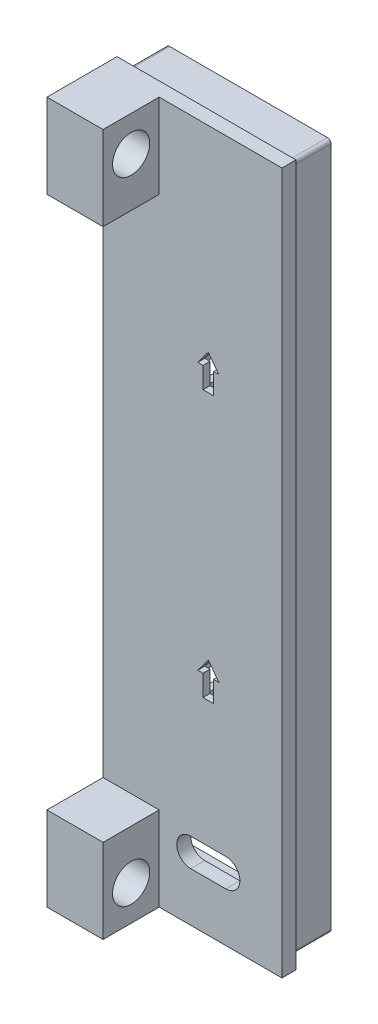
SolidWorks part; units mm, degrees
ref_plane "Front Plane" through (0, 0, 0) normal (0, 0, 1) x (1, 0, 0)
ref_plane "Top Plane" through (0, 0, 0) normal (0, 1, 0) x (1, 0, 0)
ref_plane "Right Plane" through (0, 0, 0) normal (1, 0, 0) x (0, 0, -1)
sketch "Sketch1" plane through (0, 0, 0) normal (0, 0, 1) x (1, 0, 0)
  line L0 (15.5, 38) -> (-15.5, 38) construction
  line L1 (40, 50) -> (-40, 50)
  line L2 (40, 50) -> (40, -50)
  line L3 (40, -50) -> (-40, -50)
  line L4 (-40, 50) -> (-40, -50)
  line L5 (0, 50) -> (0, -50) construction
  line L6 (15.5, 43.5) -> (15.5, 32.5)
  line L7 (15.5, -38) -> (-15.5, -38) construction
  line L260 (15.5, 43.5) -> (-15.5, 43.5)
  line L261 (15.5, 5.5) -> (-15.5, 5.5)
  line L262 (15.5, 5.5) -> (15.5, -5.5)
  line L263 (15.5, -5.5) -> (-15.5, -5.5)
  line L264 (-15.5, 5.5) -> (-15.5, -5.5)
  line L265 (0, -5.5) -> (0, 5.5) construction
  line L266 (15.5, 0) -> (-15.5, 0) construction
  line L271 (-15.5, 43.5) -> (-15.5, 32.5)
  line L272 (15.5, 32.5) -> (-15.5, 32.5)
  line L277 (15.5, -32.5) -> (15.5, -43.5)
  line L278 (15.5, -32.5) -> (-15.5, -32.5)
  line L283 (-15.5, -32.5) -> (-15.5, -43.5)
  line L284 (15.5, -43.5) -> (-15.5, -43.5)
  line L289 (25, 50) -> (25, -50) construction
  line L290 (7.7528, 32.5) -> (7.7528, 5.5) construction
  line L291 (30.5, 34.5) -> (19.5, 34.5)
  line L292 (30.5, 34.5) -> (30.5, 3.5)
  line L293 (30.5, 3.5) -> (19.5, 3.5)
  line L294 (19.5, 34.5) -> (19.5, 3.5)
  line L295 (25, 3.5) -> (25, 34.5) construction
  line L296 (30.5, 19) -> (19.5, 19) construction
  line L297 (-30.5, 3.5) -> (-19.5, 3.5)
  line L298 (-19.5, 34.5) -> (-19.5, 3.5)
  line L299 (-30.5, 34.5) -> (-19.5, 34.5)
  line L300 (-30.5, 34.5) -> (-30.5, 3.5)
  line L301 (-30.5, -34.5) -> (-30.5, -3.5)
  line L302 (-30.5, -34.5) -> (-19.5, -34.5)
  line L303 (-19.5, -34.5) -> (-19.5, -3.5)
  line L304 (-30.5, -3.5) -> (-19.5, -3.5)
  line L305 (30.5, -3.5) -> (19.5, -3.5)
  line L306 (19.5, -34.5) -> (19.5, -3.5)
  line L307 (30.5, -34.5) -> (19.5, -34.5)
  line L308 (30.5, -34.5) -> (30.5, -3.5)
  point P8 (0, 0)
  point P19 (25, 19)
  point P25 (7.7528, 19)
  dimension "D1" = 2
  dimension "D2" = 2
  dimension "D3" = 31
  dimension "D4" = 11
  dimension "D5" = 25
  dimension "D6" = 38
  dimension "D7" = 38
  dimension "D8" = 80
  dimension "D9" = 100
extrude "Boss-Extrude1" add sketch "Sketch1" along normal blind 1
sketch "Sketch2" plane through (0, 0, 1) normal (0, 0, 1) x (1, 0, 0)
  line L0 (40, 50) -> (-40, 50) construction
  line L1 (-40, 50) -> (-40, -50) construction
  line L2 (-40, -50) -> (40, -50) construction
  line L3 (40, -50) -> (40, 50) construction
  line L4 (40, 50) -> (-40, 50)
  line L5 (-40, 50) -> (-40, -50)
  line L6 (-40, -50) -> (40, -50)
  line L7 (40, -50) -> (40, 50)
extrude "back" add sketch "Sketch2" along normal blind 1
sketch "Sketch3" plane through (0, 0, 0) normal (0, 0, -1) x (-1, 0, 0)
  line L0 (-19.5, 3.5) -> (-19.5, 34.5) construction
  line L1 (-19.5, 34.5) -> (-30.5, 34.5) construction
  line L2 (-30.5, 34.5) -> (-30.5, 3.5) construction
  line L3 (-30.5, 3.5) -> (-19.5, 3.5) construction
  line L4 (15.5, -5.5) -> (15.5, 5.5) construction
  line L5 (15.5, 5.5) -> (-15.5, 5.5) construction
  line L6 (-15.5, 5.5) -> (-15.5, -5.5) construction
  line L7 (-15.5, -5.5) -> (15.5, -5.5) construction
  line L8 (-30.5, -3.5) -> (-30.5, -34.5) construction
  line L9 (-30.5, -34.5) -> (-19.5, -34.5) construction
  line L10 (-19.5, -34.5) -> (-19.5, -3.5) construction
  line L11 (-19.5, -3.5) -> (-30.5, -3.5) construction
  line L12 (-15.5, -43.5) -> (15.5, -43.5) construction
  line L13 (15.5, -43.5) -> (15.5, -32.5) construction
  line L14 (15.5, -32.5) -> (-15.5, -32.5) construction
  line L15 (-15.5, -32.5) -> (-15.5, -43.5) construction
  line L16 (19.5, -34.5) -> (30.5, -34.5) construction
  line L17 (30.5, -34.5) -> (30.5, -3.5) construction
  line L18 (30.5, -3.5) -> (19.5, -3.5) construction
  line L19 (19.5, -3.5) -> (19.5, -34.5) construction
  line L20 (30.5, 3.5) -> (30.5, 34.5) construction
  line L21 (30.5, 34.5) -> (19.5, 34.5) construction
  line L22 (19.5, 34.5) -> (19.5, 3.5) construction
  line L23 (19.5, 3.5) -> (30.5, 3.5) construction
  line L24 (-15.5, 32.5) -> (15.5, 32.5) construction
  line L25 (15.5, 32.5) -> (15.5, 43.5) construction
  line L26 (15.5, 43.5) -> (-15.5, 43.5) construction
  line L27 (-15.5, 43.5) -> (-15.5, 32.5) construction
  line L28 (15.5, -5.5) -> (15.5, 5.5)
  line L29 (15.5, 5.5) -> (-15.5, 5.5)
  line L30 (-15.5, 5.5) -> (-15.5, -5.5)
  line L31 (-15.5, -5.5) -> (15.5, -5.5)
  line L32 (-30.5, -3.5) -> (-30.5, -34.5)
  line L33 (-30.5, -34.5) -> (-19.5, -34.5)
  line L34 (-19.5, -34.5) -> (-19.5, -3.5)
  line L35 (-19.5, -3.5) -> (-30.5, -3.5)
  line L36 (-15.5, -43.5) -> (15.5, -43.5)
  line L37 (15.5, -43.5) -> (15.5, -32.5)
  line L38 (15.5, -32.5) -> (-15.5, -32.5)
  line L39 (-15.5, -32.5) -> (-15.5, -43.5)
  line L40 (19.5, -34.5) -> (30.5, -34.5)
  line L41 (30.5, -34.5) -> (30.5, -3.5)
  line L42 (30.5, -3.5) -> (19.5, -3.5)
  line L43 (19.5, -3.5) -> (19.5, -34.5)
  line L44 (30.5, 3.5) -> (30.5, 34.5)
  line L45 (30.5, 34.5) -> (19.5, 34.5)
  line L46 (19.5, 34.5) -> (19.5, 3.5)
  line L47 (19.5, 3.5) -> (30.5, 3.5)
  line L48 (-15.5, 32.5) -> (15.5, 32.5)
  line L49 (15.5, 32.5) -> (15.5, 43.5)
  line L50 (15.5, 43.5) -> (-15.5, 43.5)
  line L51 (-15.5, 43.5) -> (-15.5, 32.5)
  line L52 (-19.5, 3.5) -> (-19.5, 34.5)
  line L53 (-19.5, 34.5) -> (-30.5, 34.5)
  line L54 (-30.5, 34.5) -> (-30.5, 3.5)
  line L55 (-30.5, 3.5) -> (-19.5, 3.5)
  line L56 (-18.5, 2.5) -> (-18.5, 35.5)
  line L57 (-18.5, 35.5) -> (-31.5, 35.5)
  line L58 (-31.5, 35.5) -> (-31.5, 2.5)
  line L59 (-31.5, 2.5) -> (-18.5, 2.5)
  line L60 (-16.5, 31.5) -> (16.5, 31.5)
  line L61 (16.5, 31.5) -> (16.5, 44.5)
  line L62 (16.5, 44.5) -> (-16.5, 44.5)
  line L63 (-16.5, 44.5) -> (-16.5, 31.5)
  line L64 (31.5, 2.5) -> (31.5, 35.5)
  line L65 (31.5, 35.5) -> (18.5, 35.5)
  line L66 (18.5, 35.5) -> (18.5, 2.5)
  line L67 (18.5, 2.5) -> (31.5, 2.5)
  line L68 (16.5, -6.5) -> (16.5, 6.5)
  line L69 (16.5, 6.5) -> (-16.5, 6.5)
  line L70 (-16.5, 6.5) -> (-16.5, -6.5)
  line L71 (-16.5, -6.5) -> (16.5, -6.5)
  line L72 (-31.5, -2.5) -> (-31.5, -35.5)
  line L73 (-31.5, -35.5) -> (-18.5, -35.5)
  line L74 (-18.5, -35.5) -> (-18.5, -2.5)
  line L75 (-18.5, -2.5) -> (-31.5, -2.5)
  line L76 (-16.5, -44.5) -> (16.5, -44.5)
  line L77 (16.5, -44.5) -> (16.5, -31.5)
  line L78 (16.5, -31.5) -> (-16.5, -31.5)
  line L79 (-16.5, -31.5) -> (-16.5, -44.5)
  line L80 (18.5, -35.5) -> (31.5, -35.5)
  line L81 (31.5, -35.5) -> (31.5, -2.5)
  line L82 (31.5, -2.5) -> (18.5, -2.5)
  line L83 (18.5, -2.5) -> (18.5, -35.5)
  dimension "D1" = 1
  dimension "D2" = 1
  dimension "D3" = 1
  dimension "D4" = 1
  dimension "D5" = 1
  dimension "D6" = 1
  dimension "D7" = 1
extrude "seg masks" add sketch "Sketch3" along normal blind 6
sketch "Sketch5" plane through (0, 0, 0) normal (0, 0, -1) x (-1, 0, 0)
  line L0 (40, -50) -> (-40, -50) construction
  line L1 (40, 50) -> (40, -50) construction
  line L2 (-40, 50) -> (40, 50) construction
  line L3 (-40, -50) -> (-40, 50) construction
  line L4 (40, -50) -> (-40, -50) construction
  line L5 (40, 50) -> (40, -50) construction
  line L6 (-40, 50) -> (40, 50) construction
  line L7 (-40, -50) -> (-40, 50) construction
  line L8 (39, -49) -> (-39, -49)
  line L9 (-39, -49) -> (-39, 49)
  line L10 (-39, 49) -> (39, 49)
  line L11 (39, 49) -> (39, -49)
  line L12 (-38, 48) -> (38, 48)
  line L13 (38, 48) -> (38, -48)
  line L14 (38, -48) -> (-38, -48)
  line L15 (-38, -48) -> (-38, 48)
  dimension "D1" = 1
  dimension "D2" = 1
extrude "outer rim" add sketch "Sketch5" along normal blind 6
sketch "Sketch6" plane through (0, 0, 1) normal (0, 0, -1) x (-1, 0, 0)
  line L0 (-15.5, 38) -> (15.5, 38) construction
  line L1 (-15.5, 43.5) -> (-15.5, 32.5) construction
  line L2 (15.5, 43.5) -> (15.5, 32.5) construction
  line L3 (-1000, 0) -> (49000, 0) construction
  line L4 (25, 34.5) -> (25, -34.5) construction
  line L5 (30.5, 34.5) -> (19.5, 34.5) construction
  line L6 (19.5, -34.5) -> (30.5, -34.5) construction
  line L7 (-25, 35.5) -> (-25, -35.5) construction
  line L8 (-18.5, 35.5) -> (-31.5, 35.5) construction
  line L9 (-31.5, -35.5) -> (-18.5, -35.5) construction
  line L10 (-16.5, -38) -> (16.5, -38) construction
  line L11 (-16.5, -31.5) -> (-16.5, -44.5) construction
  line L12 (16.5, -44.5) -> (16.5, -31.5) construction
  line L20 (-31.5, 19) -> (31.5, 19) construction
  line L21 (-31.5, 35.5) -> (-31.5, 2.5) construction
  line L22 (31.5, 2.5) -> (31.5, 35.5) construction
  line L23 (-31.5, -19) -> (31.5, -19) construction
  line L24 (-31.5, -2.5) -> (-31.5, -35.5) construction
  line L25 (31.5, -35.5) -> (31.5, -2.5) construction
  line L26 (25, 22) -> (23.5, 20)
  line L27 (23.5, 20) -> (24.25, 20)
  line L28 (24.25, 20) -> (24.25, 17)
  line L29 (24.25, 17) -> (25.75, 17)
  line L30 (25.75, 20) -> (25.75, 17)
  line L31 (26.5, 20) -> (25.75, 20)
  line L32 (25, 22) -> (26.5, 20)
  line L33 (0, 44.5) -> (0, -44.5) construction
  line L34 (16.5, 44.5) -> (-16.5, 44.5) construction
  line L35 (-16.5, -44.5) -> (16.5, -44.5) construction
  line L36 (-3, 38) -> (-1, 36.5)
  line L37 (-1, 36.5) -> (-1, 37.25)
  line L38 (-1, 37.25) -> (2, 37.25)
  line L39 (2, 37.25) -> (2, 38.75)
  line L40 (-1, 38.75) -> (2, 38.75)
  line L41 (-1, 39.5) -> (-1, 38.75)
  line L42 (-3, 38) -> (-1, 39.5)
  line L43 (-24.25, 21) -> (-25.75, 21)
  line L44 (-25.75, 21) -> (-25.75, 18.5)
  line L45 (-25.75, 18.5) -> (-26.5, 18.5)
  line L46 (-26.5, 18.5) -> (-25, 16)
  line L47 (-24.25, 21) -> (-24.25, 18.5)
  line L48 (-24.25, 18.5) -> (-23.5, 18.5)
  line L49 (-23.5, 18.5) -> (-25, 16)
  line L50 (-24.25, -17) -> (-25.75, -17)
  line L51 (-25.75, -17) -> (-25.75, -20)
  line L52 (-25.75, -20) -> (-26.5, -20)
  line L53 (-26.5, -20) -> (-25, -22)
  line L54 (-23.5, -20) -> (-25, -22)
  line L55 (-24.25, -20) -> (-23.5, -20)
  line L56 (-24.25, -17) -> (-24.25, -20)
  line L57 (-2, -38.75) -> (-2, -37.25)
  line L58 (-2, -37.25) -> (1, -37.25)
  line L59 (1, -37.25) -> (1, -36.5)
  line L60 (1, -36.5) -> (3, -38)
  line L61 (1, -39.5) -> (3, -38)
  line L62 (1, -38.75) -> (1, -39.5)
  line L63 (-2, -38.75) -> (1, -38.75)
  line L64 (25, -16) -> (23.5, -18)
  line L65 (23.5, -18) -> (24.25, -18)
  line L66 (24.25, -18) -> (24.25, -21)
  line L67 (24.25, -21) -> (25.75, -21)
  line L68 (25.75, -18) -> (25.75, -21)
  line L69 (26.5, -18) -> (25.75, -18)
  line L70 (25, -16) -> (26.5, -18)
  line L71 (-0.5, 1.5) -> (-3, 0)
  line L72 (-0.5, 1.5) -> (-0.5, 0.75)
  line L73 (-0.5, 0.75) -> (2, 0.75)
  line L74 (2, 0.75) -> (2, 0)
  line L75 (2, -0.75) -> (2, 0)
  line L76 (-0.5, -0.75) -> (2, -0.75)
  line L77 (-0.5, -1.5) -> (-0.5, -0.75)
  line L78 (-0.5, -1.5) -> (-3, 0)
  point P45 (25, 17)
  point P59 (2, 38)
  point P67 (-25, 21)
  point P77 (-25, -17)
  point P85 (-2, -38)
  point P91 (25, -21)
  point P97 (2, 0.375)
  dimension "D1" = 5
  dimension "D2" = 2
  dimension "D3" = 1
  dimension "D4" = 1.5
  dimension "D5" = 0.75
  dimension "D6" = 5
  dimension "D7" = 2
  dimension "D8" = 1.5
  dimension "D9" = 1.5
  dimension "D10" = 1
  dimension "D11" = 5
  dimension "D12" = 2
  dimension "D13" = 1.5
  dimension "D14" = 1.5
  dimension "D15" = 1
  dimension "D16" = 5
  dimension "D17" = 2
  dimension "D18" = 1.5
  dimension "D19" = 3
  dimension "D20" = 1
  dimension "D21" = 5
  dimension "D22" = 2
  dimension "D23" = 1
  dimension "D24" = 1.5
  dimension "D25" = 1.5
  dimension "D26" = 5
  dimension "D27" = 1.5
  dimension "D28" = 1
  dimension "D29" = 3
  dimension "D30" = 2
  dimension "D31" = 1.5
  dimension "D32" = 5
  dimension "D33" = 2
  dimension "D34" = 1.5
  dimension "D35" = 3
  dimension "D36" = 1
extrude "direction" cut sketch "Sketch6" against normal through all both and the other way through all
sketch "Sketch7" plane through (0, 0, -6) normal (0, 0, -1) x (-1, 0, 0)
  line L0 (0, -1000) -> (0, -39.513) construction
  line L1 (-6.5, 46) -> (-3.5, 46)
  line L2 (-6.5, 46) -> (-6.5, 39.513)
  line L3 (-6.5, -46) -> (-3.5, -46)
  line L4 (-3.5, 46) -> (-3.5, 39.513)
  line L5 (16.5, 44.5) -> (-16.5, 44.5) construction
  line L6 (-16.5, -44.5) -> (16.5, -44.5) construction
  line L7 (6.5, -46) -> (3.5, -46)
  line L8 (3.5, 46) -> (3.5, 39.513)
  line L9 (6.5, 46) -> (3.5, 46)
  line L10 (6.5, 46) -> (6.5, 39.513)
  line L12 (-1025.0832, 19) -> (48974.9168, 19) construction
  line L13 (-33, 25.5) -> (-26.5, 25.5)
  line L14 (-33, 25.5) -> (-33, 22.5)
  line L15 (-33, 22.5) -> (-26.5, 22.5)
  line L16 (33, 25.5) -> (33, 22.5)
  line L17 (-31.5, 35.5) -> (-31.5, 2.5) construction
  line L18 (31.5, 2.5) -> (31.5, 35.5) construction
  line L19 (-33, 15.5) -> (-26.5, 15.5)
  line L20 (33, 12.5) -> (33, 15.5)
  line L21 (-33, 12.5) -> (-26.5, 12.5)
  line L22 (-33, 12.5) -> (-33, 15.5)
  line L23 (-33, -12.5) -> (-33, -15.5)
  line L24 (-33, -12.5) -> (-26.5, -12.5)
  line L25 (33, -12.5) -> (33, -15.5)
  line L26 (-33, -15.5) -> (-26.5, -15.5)
  line L27 (-33, -22.5) -> (-26.5, -22.5)
  line L28 (33, -25.5) -> (33, -22.5)
  line L29 (-33, -25.5) -> (-26.5, -25.5)
  line L30 (-33, -25.5) -> (-33, -22.5)
  line L31 (-6.5, 22.5) -> (-6.5, 15.5)
  line L32 (-3.5, 25.5) -> (3.5, 25.5)
  line L33 (-3.5, 22.5) -> (-3.5, 15.5)
  line L34 (-3.5, 22.5) -> (3.5, 22.5)
  line L35 (3.5, 22.5) -> (3.5, 15.5)
  line L36 (6.5, 22.5) -> (6.5, 15.5)
  line L37 (6.5, 25.5) -> (23.5, 25.5)
  line L38 (6.5, 22.5) -> (23.5, 22.5)
  line L39 (-6.5, 12.5) -> (-6.5, 1.5306)
  line L40 (-3.5, 12.5) -> (-3.5, 1.5306)
  line L41 (-3.5, 15.5) -> (3.5, 15.5)
  line L42 (-3.5, 12.5) -> (3.5, 12.5)
  line L43 (6.5, 15.5) -> (23.5, 15.5)
  line L44 (6.5, 12.5) -> (23.5, 12.5)
  line L45 (6.5, 12.5) -> (6.5, 1.5306)
  line L46 (3.5, 12.5) -> (3.5, 1.5306)
  line L47 (-6.5, -15.5) -> (-6.5, -22.5)
  line L48 (-3.5, -12.5) -> (3.5, -12.5)
  line L49 (-3.5, -15.5) -> (-3.5, -22.5)
  line L50 (-3.5, -15.5) -> (3.5, -15.5)
  line L51 (3.5, -15.5) -> (3.5, -22.5)
  line L52 (6.5, -12.5) -> (23.5, -12.5)
  line L53 (6.5, -15.5) -> (6.5, -22.5)
  line L54 (6.5, -15.5) -> (23.5, -15.5)
  line L55 (-3.5, -22.5) -> (3.5, -22.5)
  line L56 (-3.5, -25.5) -> (-3.5, -36.513)
  line L57 (-6.5, -25.5) -> (-6.5, -36.513)
  line L58 (-3.5, -25.5) -> (3.5, -25.5)
  line L59 (3.5, -25.5) -> (3.5, -36.513)
  line L60 (6.5, -22.5) -> (23.5, -22.5)
  line L61 (6.5, -25.5) -> (6.5, -36.513)
  line L62 (6.5, -25.5) -> (23.5, -25.5)
  line L63 (-18, -36.513) -> (-6.5, -36.513)
  line L64 (-18, 39.513) -> (-6.5, 39.513)
  line L65 (-18, 39.513) -> (-18, 36.513)
  line L66 (-18, 36.513) -> (-6.5, 36.513)
  line L67 (18, 39.513) -> (18, 36.513)
  line L68 (0, 36.513) -> (0, 39.513) construction
  line L69 (-18, 38.013) -> (18, 38.013) construction
  line L70 (-18, 1.5306) -> (-6.5, 1.5306)
  line L71 (-18, 1.5306) -> (-18, -1.4694)
  line L72 (-18, -1.4694) -> (-6.5, -1.4694)
  line L73 (18, 1.5306) -> (18, -1.4694)
  line L75 (-18, 0.0306) -> (18, 0.0306) construction
  line L76 (18, -39.513) -> (18, -36.513)
  line L77 (-18, -39.513) -> (-6.5, -39.513)
  line L78 (-18, -39.513) -> (-18, -36.513)
  line L79 (26.5, -37.5) -> (23.5, -37.5)
  line L80 (-26.5, 37.5) -> (-23.5, 37.5)
  line L81 (-26.5, 37.5) -> (-26.5, 25.5)
  line L82 (-26.5, -37.5) -> (-23.5, -37.5)
  line L83 (-23.5, 37.5) -> (-23.5, 25.5)
  line L84 (-25, -37.5) -> (-25, 37.5) construction
  line L86 (23.5, 37.5) -> (23.5, 25.5)
  line L87 (26.5, 37.5) -> (23.5, 37.5)
  line L88 (26.5, 37.5) -> (26.5, 25.5)
  line L89 (-3.5, 36.513) -> (3.5, 36.513)
  line L90 (-6.5, 36.513) -> (-6.5, 25.5)
  line L91 (-3.5, 36.513) -> (-3.5, 25.5)
  line L92 (-3.5, 39.513) -> (3.5, 39.513)
  line L93 (3.5, 36.513) -> (3.5, 25.5)
  line L94 (6.5, 36.513) -> (18, 36.513)
  line L95 (6.5, 36.513) -> (6.5, 25.5)
  line L96 (6.5, 39.513) -> (18, 39.513)
  line L97 (-23.5, 25.5) -> (-6.5, 25.5)
  line L98 (-23.5, 22.5) -> (-6.5, 22.5)
  line L99 (-26.5, 22.5) -> (-26.5, 15.5)
  line L100 (-23.5, 15.5) -> (-6.5, 15.5)
  line L101 (-23.5, 12.5) -> (-6.5, 12.5)
  line L102 (-26.5, 12.5) -> (-26.5, -12.5)
  line L103 (26.5, 25.5) -> (33, 25.5)
  line L104 (26.5, 22.5) -> (33, 22.5)
  line L105 (23.5, 22.5) -> (23.5, 15.5)
  line L106 (26.5, 22.5) -> (26.5, 15.5)
  line L107 (23.5, 12.5) -> (23.5, -12.5)
  line L108 (26.5, 12.5) -> (26.5, -12.5)
  line L109 (26.5, 15.5) -> (33, 15.5)
  line L110 (26.5, 12.5) -> (33, 12.5)
  line L111 (26.5, -12.5) -> (33, -12.5)
  line L112 (26.5, -15.5) -> (33, -15.5)
  line L113 (23.5, -15.5) -> (23.5, -22.5)
  line L114 (26.5, -15.5) -> (26.5, -22.5)
  line L115 (26.5, -22.5) -> (33, -22.5)
  line L116 (26.5, -25.5) -> (33, -25.5)
  line L117 (23.5, -25.5) -> (23.5, -37.5)
  line L118 (26.5, -25.5) -> (26.5, -37.5)
  line L119 (-26.5, -15.5) -> (-26.5, -22.5)
  line L120 (-23.5, -15.5) -> (-23.5, -22.5)
  line L121 (-23.5, -12.5) -> (-6.5, -12.5)
  line L122 (-23.5, -15.5) -> (-6.5, -15.5)
  line L123 (-23.5, -22.5) -> (-6.5, -22.5)
  line L124 (-23.5, -25.5) -> (-6.5, -25.5)
  line L125 (-26.5, -25.5) -> (-26.5, -37.5)
  line L126 (-23.5, -25.5) -> (-23.5, -37.5)
  line L127 (-3.5, -36.513) -> (3.5, -36.513)
  line L128 (-3.5, -39.513) -> (3.5, -39.513)
  line L129 (6.5, -36.513) -> (18, -36.513)
  line L130 (6.5, -39.513) -> (18, -39.513)
  line L131 (-6.5, -39.513) -> (-6.5, -46)
  line L132 (-3.5, -39.513) -> (-3.5, -46)
  line L134 (3.5, -39.513) -> (3.5, -46)
  line L135 (-23.5, 22.5) -> (-23.5, 15.5)
  line L136 (-23.5, 12.5) -> (-23.5, -12.5)
  line L137 (6.5, -39.513) -> (6.5, -46)
  line L140 (-3.5, 1.5306) -> (3.5, 1.5306)
  line L141 (-6.5, -1.4694) -> (-6.5, -12.5)
  line L142 (-3.5, -1.4694) -> (-3.5, -12.5)
  line L143 (-3.5, -1.4694) -> (3.5, -1.4694)
  line L144 (3.5, -1.4694) -> (3.5, -12.5)
  line L145 (6.5, -1.4694) -> (6.5, -12.5)
  line L148 (6.5, 1.5306) -> (18, 1.5306)
  line L149 (6.5, -1.4694) -> (18, -1.4694)
  point P5 (-5, 46)
  point P73 (0, 38.013)
  point P77 (0, 0.0306)
  dimension "D1" = 3
  dimension "D2" = 3.5
  dimension "D3" = 1.5
  dimension "D4" = 1.5
  dimension "D5" = 3
  dimension "D7" = 1.5
  dimension "D8" = 1.5
  dimension "D9" = 3
  dimension "D10" = 36
  dimension "D11" = 3
  dimension "D12" = 75
  dimension "D13" = 25
extrude "wire chases" cut sketch "Sketch7" against normal up to surface (6 mm away) up to face at (0, 0, 0)
sketch "Sketch8" plane through (0, 0, 0) normal (0, 0, -1) x (-1, 0, 0)
  line L0 (0, -1000) -> (0, 49000) construction
  line L3 (0, 27) -> (0, 22) construction
  line L4 (2, 27) -> (2, 22.4641)
  line L5 (-2, 27) -> (-2, 22.4641)
  arc A2 (2, 27) -> (-2, 27) centre (0, 27) ccw
  arc A4 (-2, 22.4641) -> (2, 22.4641) centre (0, 19) ccw
  point P4 (0, 22)
  dimension "D1" = 2
  dimension "D2" = 5
  dimension "D4" = 8
  dimension "D3" = 22
extrude "hanging hole" cut sketch "Sketch8" against normal through all both and the other way through all
fillet "Fillet1" radius 0.5 8 edges at (38, -48, -3) (38, 48, -3) (-38, 48, -3) (-38, -48, -3) (-39, -49, -3) (39, -49, -3) (-39, 49, -3) (39, 49, -3)
sketch "Sketch9" plane through (0, 0, 2) normal (0, 0, 1) x (1, 0, 0)
  line L1 (-40, 50) -> (-32, 50)
  line L2 (-40, 50) -> (-40, 38)
  line L3 (-40, 38) -> (-32, 38)
  line L4 (-32, 50) -> (-32, 38)
  line L5 (-40, -50) -> (-32, -50)
  line L6 (-40, -50) -> (-40, -38)
  line L7 (-40, -38) -> (-32, -38)
  line L8 (-32, -50) -> (-32, -38)
  line L9 (40, -50) -> (32, -50)
  line L10 (40, -50) -> (40, -38)
  line L11 (40, -38) -> (32, -38)
  line L12 (32, -50) -> (32, -38)
  line L13 (40, 50) -> (32, 50)
  line L14 (40, 50) -> (40, 38)
  line L15 (40, 38) -> (32, 38)
  line L16 (32, 50) -> (32, 38)
  dimension "D1" = 8
  dimension "D2" = 12
extrude "Boss-Extrude2" add sketch "Sketch9" along normal blind 8
sketch "Sketch10" plane through (40, 0, 0) normal (1, 0, 0) x (0, 0, -1)
  line L0 (-10, 38) -> (-10, 50) construction
  line L1 (-10, 50) -> (0, 50) construction
  line L5 (-1000, 0) -> (49000, 0) construction
  circle A0 centre (-6, 45) radius 1.7
  circle A1 centre (-6, -45) radius 1.7
  dimension "D1" = 3.4
  dimension "D2" = 4
  dimension "D3" = 5
extrude "Cut-Extrude1" cut sketch "Sketch10" against normal through all both and the other way through all
sketch "Sketch11" plane through (-32, 0, 0) normal (1, 0, 0) x (0, 0, -1)
  circle A0 centre (-6, 45) radius 2.65
  dimension "D1" = 5.3
extrude "Cut-Extrude2" cut sketch "Sketch11" against normal blind 3.9
mirror "Mirror1" about plane through (0, 0, 0) normal (0, 1, 0) of "Cut-Extrude2"
mirror "Mirror2" about plane through (0, 0, 0) normal (1, 0, 0) of "Cut-Extrude2"
mirror "Mirror4" about plane through (0, 0, 0) normal (1, 0, 0) of "Mirror1"
sketch "Sketch12" plane through (0, 0, 2) normal (0, 0, 1) x (1, 0, 0)
  line L1 (6.5, -15) -> (8, -15)
  line L2 (6.5, -15) -> (6.5, -22)
  line L3 (6.5, -22) -> (8, -22)
  line L4 (8, -15) -> (8, -22)
  line L5 (20.5, -15) -> (22, -15)
  line L6 (20.5, -15) -> (20.5, -22)
  line L7 (20.5, -22) -> (22, -22)
  line L8 (22, -15) -> (22, -22)
  dimension "D1" = 12.5
  dimension "D2" = 7
  dimension "D3" = 1.5
  dimension "D4" = 15
  dimension "D5" = 6.5
extrude "Boss-Extrude3" add sketch "Sketch12" along normal blind 6
sketch "Sketch13" plane through (0, 0, 2) normal (0, 0, 1) x (1, 0, 0)
  line L0 (22, -22) -> (22, -15) construction
  line L1 (6.5, -15) -> (22, -15)
  line L2 (6.5, -15) -> (6.5, -13.5)
  line L3 (6.5, -13.5) -> (22, -13.5)
  line L4 (22, -15) -> (22, -13.5)
  line L5 (6.5, -22) -> (8, -22) construction
extrude "Boss-Extrude4" add sketch "Sketch13" along normal blind 1.5
fillet "Fillet2" radius 1.5 3 edges at (22, -17.75, 2) (14.25, -13.5, 2) (6.5, -17.75, 2)
sketch "Sketch14" plane through (0, 0, 0) normal (0, 0, -1) x (-1, 0, 0)
  line L0 (-2.5, -20) -> (2.5, -20) construction
  line L1 (-2.5, -18) -> (2.5, -18)
  line L2 (-2.5, -22) -> (2.5, -22)
  line L3 (0, -1000) -> (0, 49000) construction
  arc A0 (-2.5, -18) -> (-2.5, -22) centre (-2.5, -20) ccw
  arc A1 (2.5, -22) -> (2.5, -18) centre (2.5, -20) ccw
  point P2 (0, -20)
  dimension "D2" = 2
  dimension "D1" = 20
  dimension "D3" = 5
extrude "Cut-Extrude3" cut sketch "Sketch14" against normal through all both and the other way through all
sketch "Sketch15" plane through (0, 0, 0) normal (0, 0, -1) x (-1, 0, 0)
  line L0 (16.5, 31.5) -> (16.5, 36.513) construction
  line L1 (-47.9458, 56.5995) -> (16.5, 56.5995)
  line L2 (-47.9458, 56.5995) -> (-47.9458, -57.4811)
  line L3 (-47.9458, -57.4811) -> (16.5, -57.4811)
  line L4 (16.5, 56.5995) -> (16.5, -57.4811)
extrude "Cut-Extrude4" cut sketch "Sketch15" against normal through all both and the other way through all
sketch "Sketch16" plane through (0, 0, -6) normal (0, 0, -1) x (-1, 0, 0)
  line L0 (40, -50) -> (16.5, -50) construction
  line L1 (16.5, 50) -> (14.5, 50)
  line L2 (16.5, 50) -> (16.5, -50)
  line L3 (16.5, -50) -> (14.5, -50)
  line L4 (14.5, 50) -> (14.5, -50)
  dimension "D1" = 2
extrude "Boss-Extrude5" add sketch "Sketch16" against normal up to surface (8 mm away) up to face at (-30.125, 0, 2)
sketch "Sketch17" plane through (0, 0, 0) normal (0, 0, -1) x (-1, 0, 0)
  line L0 (22.5, -41) -> (27.5, -41) construction
  line L1 (22.5, -39) -> (27.5, -39)
  line L2 (22.5, -43) -> (27.5, -43)
  line L3 (30.5, -34.5) -> (19.5, -34.5) construction
  arc A0 (22.5, -39) -> (22.5, -43) centre (22.5, -41) ccw
  arc A1 (27.5, -43) -> (27.5, -39) centre (27.5, -41) ccw
  point P2 (25, -41)
  point P9 (25, -34.5)
  dimension "D3" = 2
  dimension "D1" = 0
  dimension "D2" = 5
  dimension "D4" = 6.5
extrude "Cut-Extrude5" cut sketch "Sketch17" against normal through all both and the other way through all
sketch "Sketch18" plane through (0, 0, -6) normal (0, 0, -1) x (-1, 0, 0)
  line L0 (14.5, -50) -> (16.5, -50) construction
  line L1 (14.5, 50) -> (15.5, 50)
  line L2 (14.5, 50) -> (14.5, -50)
  line L3 (14.5, -50) -> (15.5, -50)
  line L4 (15.5, 49) -> (15.5, -49)
  line L6 (16.5, 49) -> (15.5, 49)
  line L7 (16.5, 49) -> (16.5, 50)
  line L8 (16.5, 50) -> (15.5, 50)
  line L10 (16.5, -49) -> (15.5, -49)
  line L11 (16.5, -49) -> (16.5, -50)
  line L12 (16.5, -50) -> (15.5, -50)
extrude "Cut-Extrude6" cut sketch "Sketch18" against normal up to surface (6 mm away) up to face at (-30.1207, 0, 0)
fillet "Fillet3" radius 0.5 2 edges at (-15.5, -49, -3) (-15.5, 49, -3)
